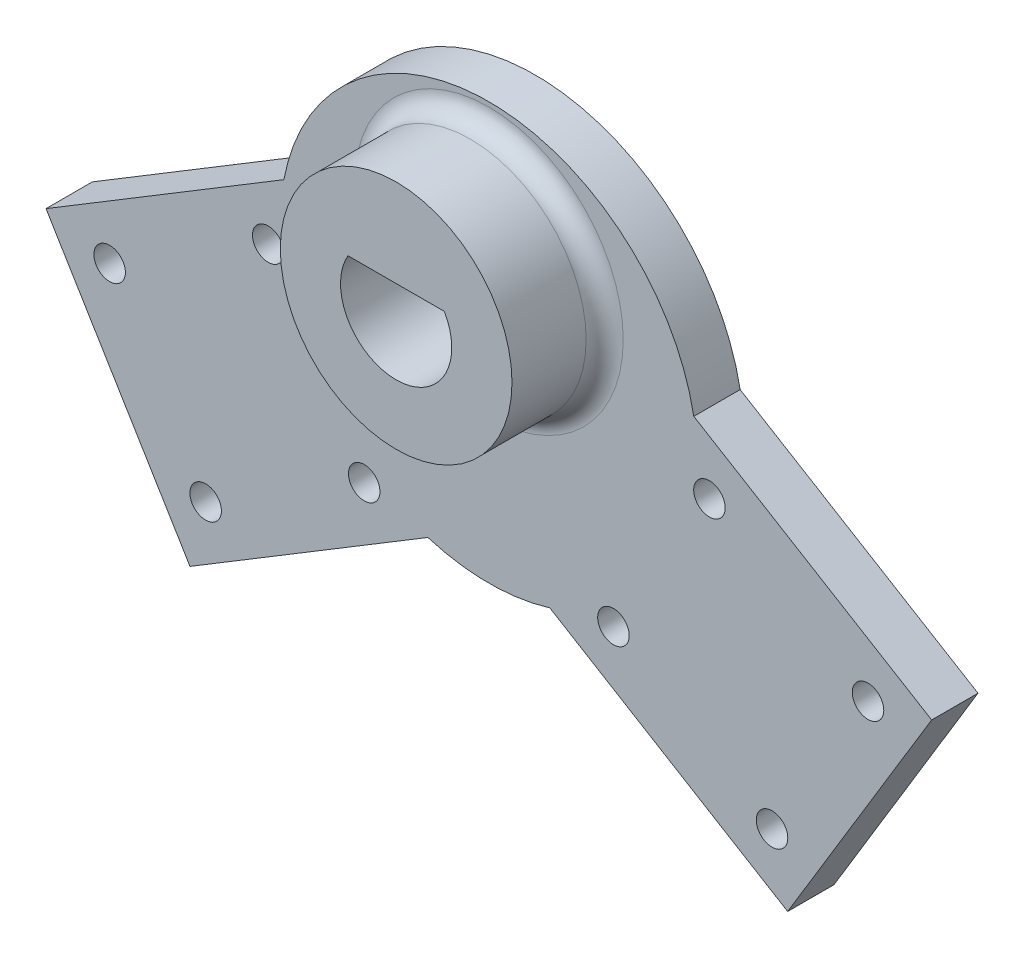
SolidWorks part; units mm, degrees
material "PLA 15%"
ref_plane "Front Plane" through (0, 0, 0) normal (0, 0, 1) x (1, 0, 0)
ref_plane "Top Plane" through (0, 0, 0) normal (0, 1, 0) x (1, 0, 0)
ref_plane "Right Plane" through (0, 0, 0) normal (1, 0, 0) x (0, 0, -1)
sketch "Sketch2" plane through (0, 0, 0) normal (0, 0, 1) x (1, 0, 0)
  line L8 (0, 0) -> (0, -22.5) construction
  line L9 (0, 0) -> (6.5784, -21.5169) construction
  line L10 (0, 0) -> (-6.5784, -21.5169) construction
  line L11 (6.5784, -21.5169) -> (22.1146, 4.1469)
  line L12 (6.5784, -21.5169) -> (32.2421, -37.053)
  line L13 (22.1146, 4.1469) -> (47.7783, -11.3893)
  line L14 (32.2421, -37.053) -> (47.7783, -11.3893)
  line L15 (-6.5784, -21.5169) -> (-22.1146, 4.1469)
  line L16 (-6.5784, -21.5169) -> (-32.2421, -37.053)
  line L17 (-22.1146, 4.1469) -> (-47.7783, -11.3893)
  line L18 (-32.2421, -37.053) -> (-47.7783, -11.3893)
  line L19 (-15.6807, -16.1358) -> (-21.5667, -6.4129) construction
  line L20 (-23.8025, -2.7198) -> (-40.9116, -13.0772) construction
  line L21 (-30.5542, -30.1864) -> (-40.9116, -13.0772) construction
  line L22 (-13.445, -19.8289) -> (-30.5542, -30.1864) construction
  line L23 (13.445, -19.8289) -> (15.6807, -16.1358) construction
  line L24 (23.8025, -2.7198) -> (40.9116, -13.0772) construction
  line L25 (30.5542, -30.1864) -> (40.9116, -13.0772) construction
  line L26 (13.445, -19.8289) -> (30.5542, -30.1864) construction
  line L27 (-21.5667, -6.4129) -> (-23.8025, -2.7198) construction
  line L28 (-13.445, -19.8289) -> (-23.8025, -2.7198) construction
  line L29 (-13.445, -19.8289) -> (-15.6807, -16.1358) construction
  line L30 (15.6807, -16.1358) -> (21.5667, -6.4129) construction
  line L31 (21.5667, -6.4129) -> (23.8025, -2.7198) construction
  line L32 (13.445, -19.8289) -> (23.8025, -2.7198) construction
  line L33 (0, 22.5) -> (0, -22.5) construction
  line L34 (5.1962, 10.5) -> (-5.1962, 10.5)
  arc A0 (-21.5667, -6.4129) -> (-15.6807, -16.1358) centre (0, 0) ccw construction
  arc A1 (-22.1146, 4.1469) -> (-21.5667, -6.4129) centre (0, 0) ccw construction
  arc A2 (-15.6807, -16.1358) -> (-6.5784, -21.5169) centre (0, 0) ccw construction
  arc A3 (-6.5784, -21.5169) -> (6.5784, -21.5169) centre (0, 0) ccw
  arc A4 (15.6807, -16.1358) -> (21.5667, -6.4129) centre (0, 0) ccw construction
  arc A5 (22.1146, 4.1469) -> (-22.1146, 4.1469) centre (0, 0) ccw
  arc A6 (21.5667, -6.4129) -> (22.1146, 4.1469) centre (0, 0) ccw construction
  arc A7 (6.5784, -21.5169) -> (15.6807, -16.1358) centre (0, 0) ccw construction
  arc A8 (-5.1962, 10.5) -> (5.1962, 10.5) centre (0, 7.5) ccw
  arc A9 (-5.1962, 10.5) -> (5.1962, 10.5) centre (0, 7.5) cw construction
  circle A10 centre (0, 7.5) radius 12.5
  point P28 (0, 13.5)
  dimension "D5" = 45
  dimension "D10" = 6
  dimension "D12" = 25
  dimension "D1" = 17
  dimension "D2" = 17
  dimension "D3" = 30
  dimension "D4" = 30
  dimension "D6" = 30
  dimension "D7" = 30
  dimension "D9" = 30
  dimension "D11" = 3
  dimension "D8" = 5
extrude "Boss-Extrude1" add sketch "Sketch2" along normal blind 5 contours L13 A5 L17 L18 L16 A3 L12 L14 A8 L34 | L18 L16 L15 L17 | L12 L14 L13 L11 | A10 A8 L34
hole_wizard "M3 Clearance Hole1" positions "Sketch5" profile "Sketch6" hole size "M3" standard "ANSI Metric" end condition through all
sketch "Sketch5" plane through (0, 0, 5) normal (0, 0, 1) x (1, 0, 0)
  point P0 (-40.9116, -13.0772)
  point P3 (-23.8025, -2.7198)
  point P6 (-13.445, -19.8289)
  point P9 (-30.5542, -30.1864)
  point P12 (13.445, -19.8289)
  point P15 (23.8025, -2.7198)
  point P18 (40.9116, -13.0772)
  point P21 (30.5542, -30.1864)
sketch "Sketch6" plane through (-40.9116, -13.0772, 5) normal (1, 0, 0) x (0, -1, 0)
  line L0 (0, 0) -> (0, 5)
  line L1 (0, 5) -> (1.7, 5)
  line L2 (1.7, 5) -> (1.7, 0)
  line L5 (1.7, 0) -> (0, 0)
  line L11 (0, -6.35) -> (0, 107.95) construction
  dimension "Thru Hole Dia." = 3.4
  dimension "Thru Hole Depth" = 5
extrude "Boss-Extrude3" add sketch "Sketch2<6>" along normal blind 10 from surface contours A10 A8 L34 region at (-12.1464, 7.5, 0) starting at face at (-39.2116, -13.0772, 5)
sketch "Sketch2<6>" plane through (0, 0, 0) normal (0, 0, 1) x (1, 0, 0) same geometry as "Sketch2"
fillet "Fillet1" radius 2 1 edges at (12.5, 7.5, 5)
equation "\"dshaftdistance\"= 0.25"
